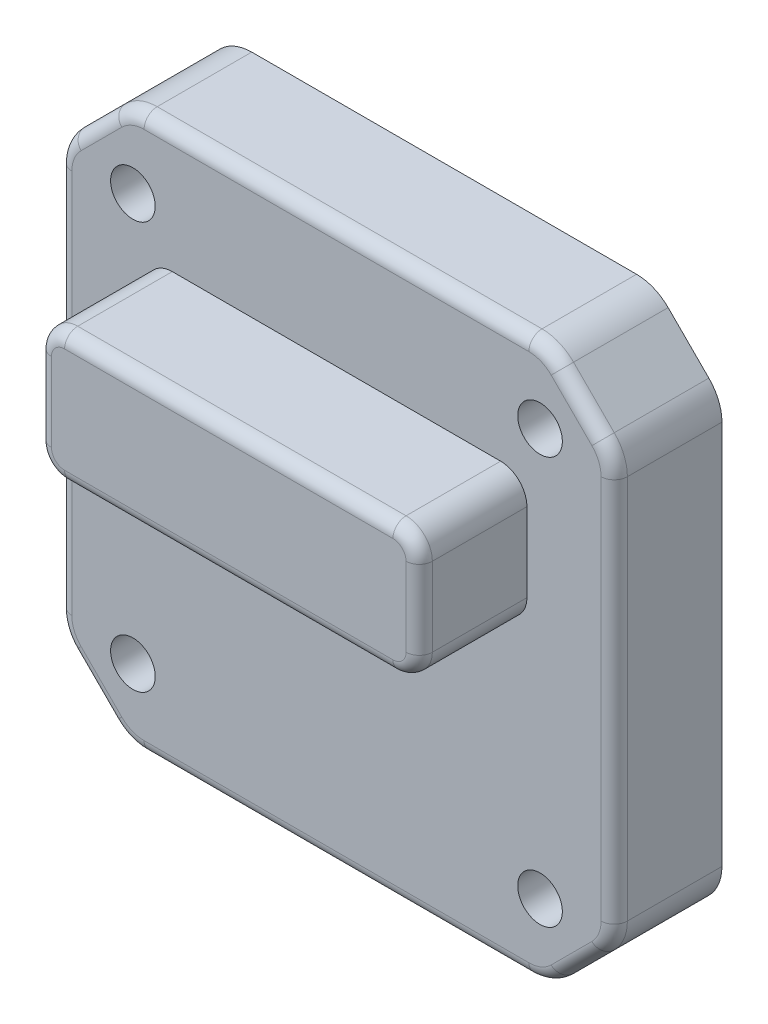
SolidWorks part; units mm, degrees
material "6061 Alloy"
ref_plane "Front Plane" through (0, 0, 0) normal (0, 0, 1) x (1, 0, 0)
ref_plane "Top Plane" through (0, 0, 0) normal (0, 1, 0) x (1, 0, 0)
ref_plane "Right Plane" through (0, 0, 0) normal (1, 0, 0) x (0, 0, -1)
sketch "Sketch1" plane through (0, 0, 0) normal (0, 0, 1) x (1, 0, 0)
  line L0 (-21.15, 14.65) -> (-21.15, -14.65)
  line L1 (-20.1542, -17.0542) -> (-17.0542, -20.1542)
  line L2 (-14.65, -21.15) -> (14.65, -21.15)
  line L3 (17.0542, -20.1542) -> (20.1542, -17.0542)
  line L4 (21.15, -14.65) -> (21.15, 14.65)
  line L5 (20.1542, 17.0542) -> (17.0542, 20.1542)
  line L6 (14.65, 21.15) -> (-14.65, 21.15)
  line L7 (-17.0542, 20.1542) -> (-20.1542, 17.0542)
  line L8 (-21.15, 0) -> (21.15, 0) construction
  line L9 (0, 21.15) -> (0, -21.15) construction
  line L11 (-15.5, -15.5) -> (15.5, -15.5) construction
  line L12 (-15.5, -15.5) -> (-15.5, 15.5) construction
  line L13 (-15.5, 15.5) -> (15.5, 15.5) construction
  line L14 (15.5, -15.5) -> (15.5, 15.5) construction
  line L15 (-15.5, -15.5) -> (15.5, 15.5) construction
  line L16 (-15.5, 15.5) -> (15.5, -15.5) construction
  circle A0 centre (-15.5, 15.5) radius 1.7
  circle A1 centre (15.5, 15.5) radius 1.7
  circle A2 centre (15.5, -15.5) radius 1.7
  circle A3 centre (-15.5, -15.5) radius 1.7
  arc A4 (21.15, 14.65) -> (20.1542, 17.0542) centre (17.75, 14.65) ccw
  arc A5 (17.0542, 20.1542) -> (14.65, 21.15) centre (14.65, 17.75) ccw
  arc A6 (20.1542, -17.0542) -> (21.15, -14.65) centre (17.75, -14.65) ccw
  arc A7 (14.65, -21.15) -> (17.0542, -20.1542) centre (14.65, -17.75) ccw
  arc A8 (-17.0542, -20.1542) -> (-14.65, -21.15) centre (-14.65, -17.75) ccw
  arc A9 (-21.15, -14.65) -> (-20.1542, -17.0542) centre (-17.75, -14.65) ccw
  arc A10 (-21.15, 14.65) -> (-20.1542, 17.0542) centre (-17.75, 14.65) cw
  arc A11 (-14.65, 21.15) -> (-17.0542, 20.1542) centre (-14.65, 17.75) ccw
  point P12 (0, 0)
  dimension "D3" = 3.4
  dimension "D4" = 3.4
  dimension "D1" = 42.3
  dimension "D2" = 31
  dimension "D5" = 6.5
extrude "Boss-Extrude1" add sketch "Sketch1" along normal blind 8.2
sketch "Sketch2" plane through (0, 0, 8.2) normal (0, 0, 1) x (1, 0, 0)
  line L0 (0, 0) -> (0, 1.849) construction
  line L1 (-14.5, 11.849) -> (14.5, 11.849)
  line L2 (-14.5, 11.849) -> (-14.5, 1.849)
  line L3 (-14.5, 1.849) -> (14.5, 1.849)
  line L4 (14.5, 11.849) -> (14.5, 1.849)
  dimension "D1" = 29
  dimension "D2" = 10
extrude "Boss-Extrude2" add sketch "Sketch2" along normal blind 8.2
fillet "Fillet2" radius 1 20 edges at (-20.8912, 15.9511, 8.2) (-18.6042, 18.6042, 8.2) (-15.9511, 20.8912, 8.2) (0, 21.15, 8.2) (15.9511, 20.8912, 8.2) (18.6042, 18.6042, 8.2) (20.8912, 15.9511, 8.2) (21.15, 0, 8.2) (20.8912, -15.9511, 8.2) (18.6042, -18.6042, 8.2) (15.9511, -20.8912, 8.2) (0, -21.15, 8.2) (-15.9511, -20.8912, 8.2) (-18.6042, -18.6042, 8.2) (-20.8912, -15.9511, 8.2) (0, 11.849, 16.4) (14.5, 6.849, 16.4) (0, 1.849, 16.4) (-14.5, 6.849, 16.4) (-21.15, 0, 8.2)
fillet "Fillet3" radius 2 8 edges at (-14.2071, 11.5562, 16.1071) (-14.2071, 2.1419, 16.1071) (14.2071, 2.1419, 16.1071) (14.2071, 11.5562, 16.1071) (14.5, 11.849, 11.8) (14.5, 1.849, 11.8) (-14.5, 1.849, 11.8) (-14.5, 11.849, 11.8)
